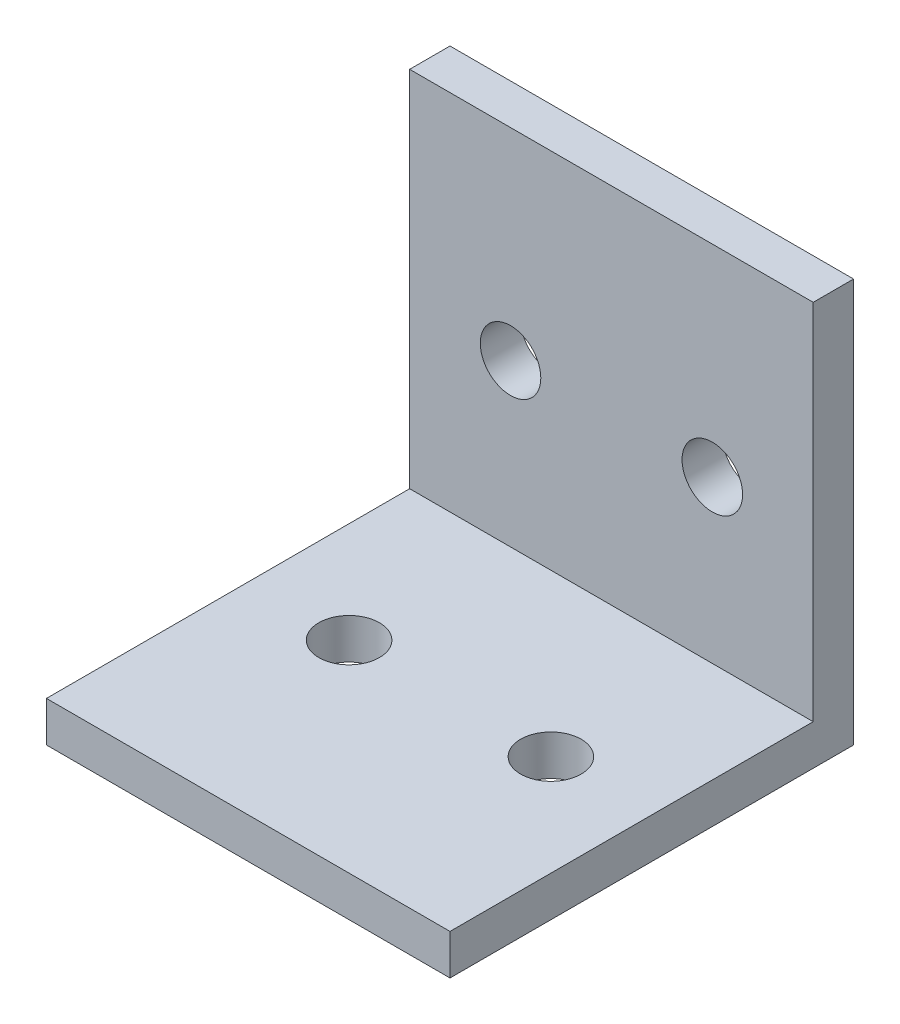
SolidWorks part; units mm, degrees
ref_plane "前视基准面" through (0, 0, 0) normal (0, 0, 1) x (1, 0, 0)
ref_plane "上视基准面" through (0, 0, 0) normal (0, 1, 0) x (1, 0, 0)
ref_plane "右视基准面" through (0, 0, 0) normal (1, 0, 0) x (0, 0, -1)
sketch "草图1" plane through (0, 0, 0) normal (0, 0, 1) x (1, 0, 0)
  line L1 (-10, 10) -> (10, 10)
  line L2 (-10, 10) -> (-10, -10)
  line L3 (-10, -10) -> (10, -10)
  line L4 (10, 10) -> (10, -10)
  line L5 (-10, 10) -> (10, -10) construction
  line L6 (-10, -10) -> (10, 10) construction
  point P0 (0, 0)
  dimension "D1" = 20
  dimension "D2" = 20
extrude "凸台-拉伸1" add sketch "草图1" along normal blind 2
sketch "草图2" plane through (0, 0, 2) normal (0, 0, 1) x (1, 0, 0)
  line L0 (10, -10) -> (10, 10) construction
  line L1 (-10, -10) -> (10, -10)
  line L2 (-10, -10) -> (-10, -8)
  line L3 (-10, -8) -> (10, -8)
  line L4 (10, -10) -> (10, -8)
  dimension "D1" = 2
extrude "凸台-拉伸2" add sketch "草图2" along normal blind 18
sketch "草图4" plane through (0, -10, 0) normal (0, -1, 0) x (1, 0, 0)
  line L0 (-10, 20) -> (-10, 0) construction
  line L1 (10, 20) -> (10, 0) construction
  line L2 (-10, 20) -> (10, 20) construction
  circle A0 centre (-5, 10) radius 1.5
  circle A1 centre (5, 10) radius 1.5
  dimension "D1" = 3
  dimension "D2" = 3
  dimension "D3" = 5
  dimension "D4" = 5
  dimension "D5" = 10
extrude "切除-拉伸1" cut sketch "草图4" against normal blind 18
sketch "草图5" plane through (0, 0, 0) normal (0, 0, -1) x (-1, 0, 0)
sketch "草图6" plane through (0, 0, 0) normal (0, 0, -1) x (-1, 0, 0)
  line L0 (-10, -10) -> (-10, 10) construction
  line L1 (10, 10) -> (10, -10) construction
  line L2 (10, -10) -> (-10, -10) construction
  circle A0 centre (5, 0) radius 1.5
  circle A1 centre (-5, 0) radius 1.5
  dimension "D1" = 3
  dimension "D2" = 3
  dimension "D3" = 5
  dimension "D4" = 5
  dimension "D5" = 10
extrude "切除-拉伸2" cut sketch "草图6" against normal blind 18
